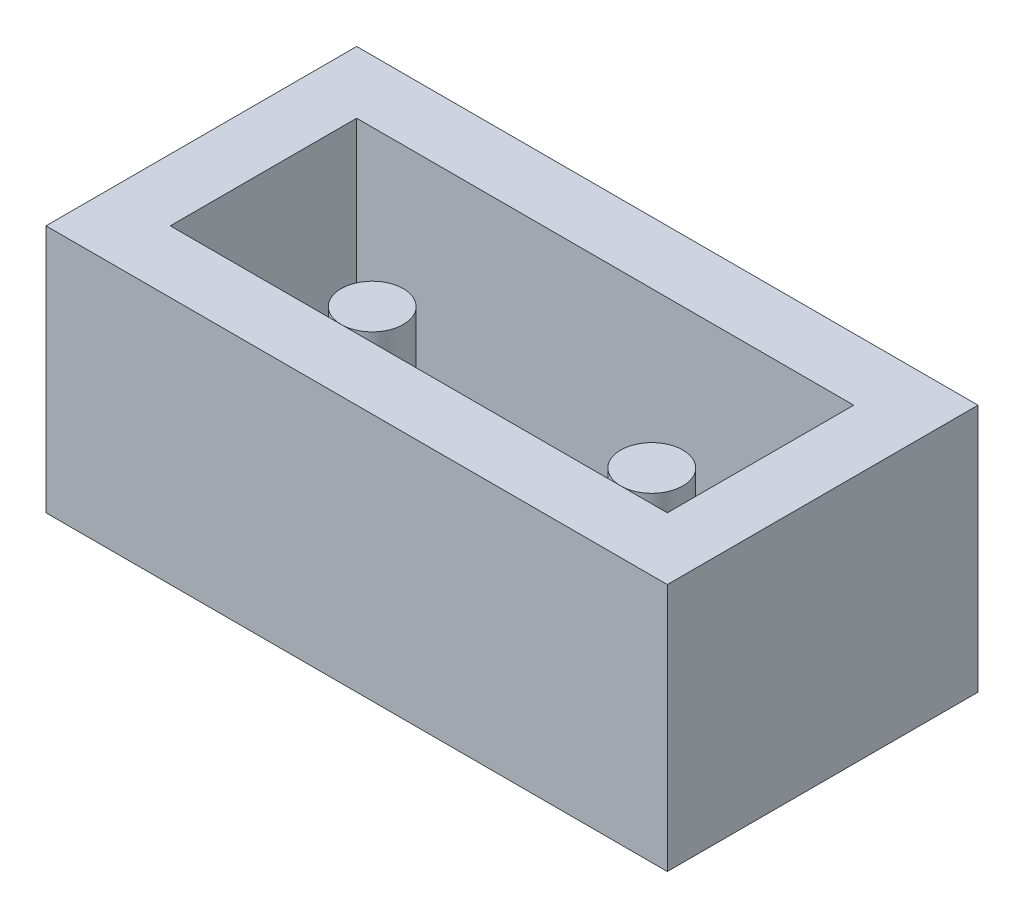
SolidWorks part; units mm, degrees
ref_plane "前视基准面" through (0, 0, 0) normal (0, 0, 1) x (1, 0, 0)
ref_plane "上视基准面" through (0, 0, 0) normal (0, 1, 0) x (1, 0, 0)
ref_plane "右视基准面" through (0, 0, 0) normal (1, 0, 0) x (0, 0, -1)
sketch "草图1" plane through (0, 0, 0) normal (0, 1, 0) x (1, 0, 0)
  line L1 (4, -1.5) -> (-4, -1.5)
  line L2 (4, -1.5) -> (4, 1.5)
  line L3 (4, 1.5) -> (-4, 1.5)
  line L4 (-4, -1.5) -> (-4, 1.5)
  line L5 (4, -1.5) -> (-4, 1.5) construction
  line L6 (4, 1.5) -> (-4, -1.5) construction
  point P0 (0, 0)
  dimension "D1" = 8
  dimension "D2" = 3
extrude "凸台-拉伸1" add sketch "草图1" along normal blind 1
sketch "草图2" plane through (0, 1, 0) normal (0, 1, 0) x (1, 0, 0)
  line L0 (0, 0) -> (0, 0.9954) construction
  circle A0 centre (-2.25, 0) radius 0.5
  circle A1 centre (2.25, 0) radius 0.5
  dimension "D1" = 1
  dimension "D2" = 4.5
extrude "凸台-拉伸2" add sketch "草图2" along normal blind 3
sketch "草图3" plane through (0, 1, 0) normal (0, 1, 0) x (1, 0, 0)
  line L0 (-5, 2.5) -> (-5, -2.5)
  line L1 (-5, -2.5) -> (5, -2.5)
  line L2 (5, -2.5) -> (5, 2.5)
  line L3 (5, 2.5) -> (-5, 2.5)
  line L4 (-4, 1.5) -> (-4, -1.5)
  line L5 (-4, -1.5) -> (4, -1.5)
  line L6 (4, -1.5) -> (4, 1.5)
  line L7 (4, 1.5) -> (-4, 1.5)
  line L8 (-4, 1.5) -> (-4, -1.5)
  line L9 (-4, -1.5) -> (4, -1.5)
  line L10 (4, -1.5) -> (4, 1.5)
  line L11 (4, 1.5) -> (-4, 1.5)
  dimension "D1" = 0
  dimension "D2" = 1
extrude "凸台-拉伸3" add sketch "草图3" along normal blind 4 separate body
sketch "草图4" plane through (0, 4, 0) normal (0, 1, 0) x (1, 0, 0)
  point P0 (-2.25, 0)
  point P1 (2.25, 0)
other "连接点1" parameters "直径"=2, "端头长度"=1
ref_axis "基准轴1" through (-2.25, 14, 0) along (0, -1, 0)
other "连接点2" parameters "直径"=2, "端头长度"=1
ref_axis "基准轴2" through (2.25, 14, 0) along (0, -1, 0)
